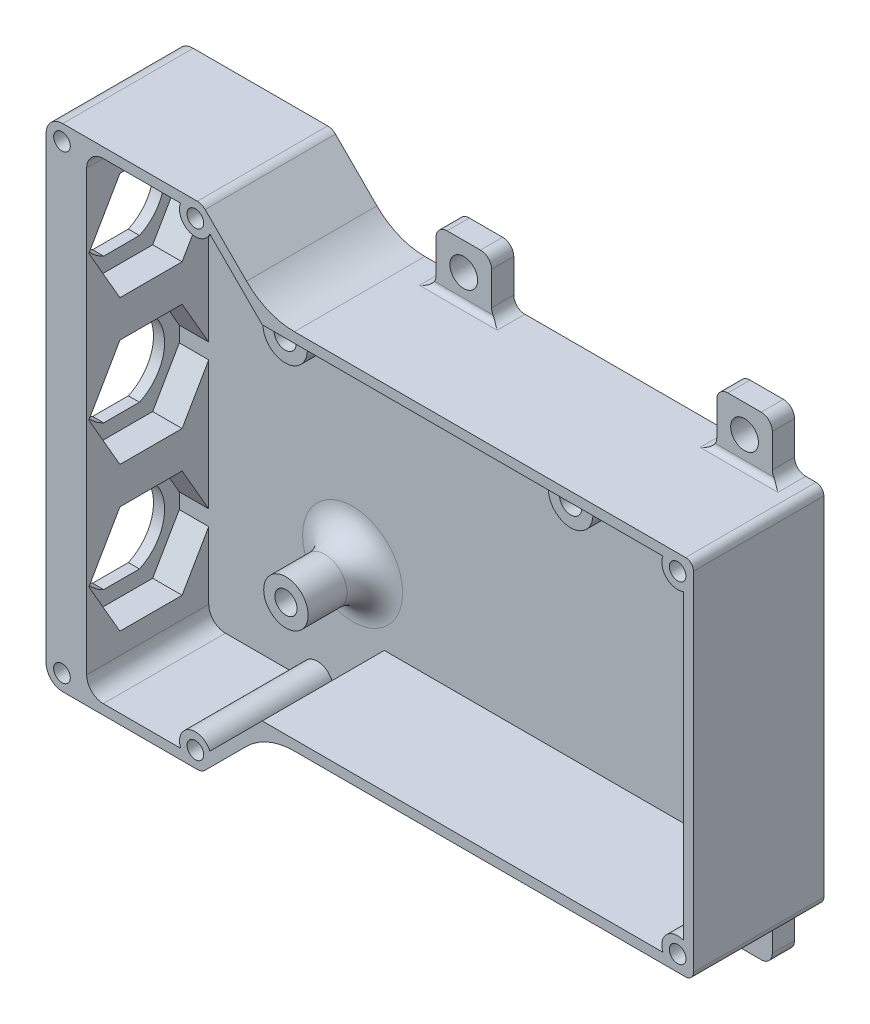
SolidWorks part; units mm, degrees
ref_plane "Front Plane" through (0, 0, 0) normal (0, 0, 1) x (1, 0, 0)
ref_plane "Top Plane" through (0, 0, 0) normal (0, 1, 0) x (1, 0, 0)
ref_plane "Right Plane" through (0, 0, 0) normal (1, 0, 0) x (0, 0, -1)
sketch "Sketch1" plane through (0, 0, 0) normal (0, 0, 1) x (1, 0, 0)
  line L0 (21.6569, -104.2696) -> (33.2669, -92.6596)
  line L1 (21.6569, -11.2696) -> (33.2619, -22.8746)
  line L2 (22.8284, -103.098) -> (34.4384, -91.488) construction
  line L3 (22.8284, -12.4412) -> (34.4334, -24.0462) construction
  line L10 (0, -100.2696) -> (20, -100.2696)
  line L11 (0, -15.2696) -> (20, -15.2696)
  line L12 (20, -100.2696) -> (31.61, -88.6596)
  line L13 (96.455, -88.6596) -> (8, -88.6596) construction
  line L14 (8, -26.8746) -> (96.455, -26.8746) construction
  line L15 (20, -15.2696) -> (31.605, -26.8746)
  line L16 (1.6569, -104.2696) -> (21.6569, -104.2696)
  line L17 (1.6569, -11.2696) -> (21.6569, -11.2696)
  line L24 (96.455, -88.6596) -> (31.61, -88.6596)
  line L26 (31.605, -26.8746) -> (96.455, -26.8746)
  line L27 (96.455, -26.8746) -> (96.455, -88.6596)
  line L28 (100.455, -92.6596) -> (33.2669, -92.6596)
  line L29 (33.2619, -22.8746) -> (100.455, -22.8746)
  line L31 (100.455, -22.8746) -> (100.455, -92.6596)
  line L33 (0, -100.2696) -> (-18.3, -100.2696)
  line L35 (0, -15.2696) -> (-18.3, -15.2696)
  line L36 (-18.3, -15.2696) -> (-18.3, -11.2696)
  line L37 (-18.3, -11.2696) -> (1.6569, -11.2696)
  line L38 (-18.3, -100.2696) -> (-18.3, -104.2696)
  line L39 (-18.3, -104.2696) -> (1.6569, -104.2696)
  line L45 (100.455, -92.6596) -> (4, -92.6596) construction
  line L46 (4, -92.6596) -> (4, -22.8746) construction
  line L47 (4, -22.8746) -> (100.455, -22.8746) construction
  line L52 (8, -88.6596) -> (8, -26.8746) construction
  dimension "D1" = 4
  dimension "D3" = 4
  dimension "D2" = 4
extrude "Boss-Extrude1" add sketch "Sketch1" along normal blind 36.78
sketch "Sketch2" plane through (0, 0, 0) normal (0, 0, -1) x (-1, 0, 0)
  line L0 (18.3, -15.2696) -> (18.3, -100.2696)
  line L16 (-33.2669, -92.6596) -> (-21.6569, -104.2696)
  line L17 (-31.61, -88.6596) -> (-96.455, -88.6596)
  line L18 (-96.455, -88.6596) -> (-96.455, -26.8746)
  line L19 (-96.455, -26.8746) -> (-31.605, -26.8746)
  line L20 (-33.2669, -92.6596) -> (-21.6569, -104.2696)
  line L21 (-20, -15.2696) -> (18.3, -15.2696)
  line L22 (18.3, -15.2696) -> (18.3, -11.2696)
  line L23 (18.3, -11.2696) -> (-21.6569, -11.2696)
  line L24 (-20, -100.2696) -> (-31.61, -88.6596)
  line L25 (-33.2619, -22.8746) -> (-100.455, -22.8746)
  line L26 (-100.455, -22.8746) -> (-100.455, -92.6596)
  line L27 (-100.455, -92.6596) -> (-33.2669, -92.6596)
  line L29 (-21.6569, -104.2696) -> (18.3, -104.2696)
  line L30 (18.3, -104.2696) -> (18.3, -100.2696)
  line L31 (18.3, -100.2696) -> (-20, -100.2696)
  line L33 (-31.605, -26.8746) -> (-20, -15.2696)
  line L35 (-21.6569, -11.2696) -> (-33.2619, -22.8746)
  line L36 (-21.6569, -11.2696) -> (-33.2619, -22.8746)
  line L38 (18.3, -15.2696) -> (18.3, -11.2696)
  line L39 (18.3, -11.2696) -> (-21.6569, -11.2696)
  line L41 (-33.2619, -22.8746) -> (-100.455, -22.8746)
  line L42 (-100.455, -22.8746) -> (-100.455, -92.6596)
  line L43 (-100.455, -92.6596) -> (-33.2669, -92.6596)
  line L45 (-21.6569, -104.2696) -> (18.3, -104.2696)
  line L46 (18.3, -104.2696) -> (18.3, -100.2696)
  dimension "D1" = 0
extrude "Boss-Extrude2" add sketch "Sketch2" against normal blind 3.5
sketch "Sketch4" plane through (-5.3, 0, 0) normal (1, 0, 0) x (0, 0, -1)
  line L0 (-13.8923, -90.5196) -> (-10.7395, -90.5196) construction
  line L1 (-13.8923, -90.5196) -> (-17.0451, -90.5196) construction
  line L2 (-13.8923, -77.0196) -> (-10.7395, -77.0196) construction
  line L3 (-13.8923, -77.0196) -> (-17.0451, -77.0196) construction
  line L4 (-13.8923, -64.5196) -> (-10.7395, -64.5196) construction
  line L5 (-13.8923, -64.5196) -> (-17.0451, -64.5196) construction
  line L6 (-13.8923, -51.0196) -> (-10.7395, -51.0196) construction
  line L7 (-13.8923, -51.0196) -> (-17.0451, -51.0196) construction
  line L8 (-13.8923, -38.5196) -> (-17.0451, -38.5196) construction
  line L9 (-13.8923, -38.5196) -> (-10.7395, -38.5196) construction
  line L10 (-13.8923, -25.0196) -> (-10.7395, -25.0196) construction
  line L11 (-13.8923, -25.0196) -> (-17.0451, -25.0196) construction
  line L12 (-13.8923, -90.5196) -> (-10.7395, -90.5196)
  line L13 (-13.8923, -90.5196) -> (-17.0451, -90.5196)
  line L14 (-13.8923, -77.0196) -> (-10.7395, -77.0196)
  line L15 (-13.8923, -77.0196) -> (-17.0451, -77.0196)
  line L16 (-13.8923, -64.5196) -> (-10.7395, -64.5196)
  line L17 (-13.8923, -64.5196) -> (-17.0451, -64.5196)
  line L18 (-13.8923, -51.0196) -> (-10.7395, -51.0196)
  line L19 (-13.8923, -51.0196) -> (-17.0451, -51.0196)
  line L20 (-13.8923, -38.5196) -> (-17.0451, -38.5196)
  line L21 (-13.8923, -38.5196) -> (-10.7395, -38.5196)
  line L22 (-13.8923, -25.0196) -> (-10.7395, -25.0196)
  line L23 (-13.8923, -25.0196) -> (-17.0451, -25.0196)
  line L24 (-13.8923, -38.8196) -> (-17.111, -38.8196)
  line L25 (-13.8923, -38.8196) -> (-10.6736, -38.8196)
  line L26 (-13.8923, -24.7196) -> (-10.6736, -24.7196)
  line L27 (-13.8923, -24.7196) -> (-17.111, -24.7196)
  line L28 (-13.8923, -64.8196) -> (-17.111, -64.8196)
  line L29 (-13.8923, -64.8196) -> (-10.6736, -64.8196)
  line L30 (-13.8923, -50.7196) -> (-10.6736, -50.7196)
  line L31 (-13.8923, -50.7196) -> (-17.111, -50.7196)
  line L32 (-13.8923, -90.8196) -> (-17.111, -90.8196)
  line L33 (-13.8923, -90.8196) -> (-10.6736, -90.8196)
  line L34 (-13.8923, -76.7196) -> (-10.6736, -76.7196)
  line L35 (-13.8923, -76.7196) -> (-17.111, -76.7196)
  line L36 (-36.78, -100.2696) -> (-3.5, -100.2696)
  line L37 (-36.78, -100.2696) -> (-3.5, -100.2696)
  line L38 (-3.5, -100.2696) -> (-3.5, -15.2696)
  line L39 (-3.5, -100.2696) -> (-3.5, -15.2696)
  line L40 (-3.5, -15.2696) -> (-36.78, -15.2696)
  line L41 (-3.5, -15.2696) -> (-36.78, -15.2696)
  line L42 (-36.78, -15.2696) -> (-36.78, -100.2696)
  arc A0 (-17.0451, -77.0196) -> (-17.0451, -90.5196) centre (-13.8923, -83.7696) ccw construction
  arc A1 (-10.7395, -90.5196) -> (-10.7395, -77.0196) centre (-13.8923, -83.7696) ccw construction
  arc A2 (-10.7395, -64.5196) -> (-10.7395, -51.0196) centre (-13.8923, -57.7696) ccw construction
  arc A3 (-17.0451, -51.0196) -> (-17.0451, -64.5196) centre (-13.8923, -57.7696) ccw construction
  arc A4 (-17.0451, -25.0196) -> (-17.0451, -38.5196) centre (-13.8923, -31.7696) ccw construction
  arc A5 (-10.7395, -38.5196) -> (-10.7395, -25.0196) centre (-13.8923, -31.7696) ccw construction
  arc A6 (-17.0451, -77.0196) -> (-17.0451, -90.5196) centre (-13.8923, -83.7696) ccw
  arc A7 (-10.7395, -90.5196) -> (-10.7395, -77.0196) centre (-13.8923, -83.7696) ccw
  arc A8 (-10.7395, -64.5196) -> (-10.7395, -51.0196) centre (-13.8923, -57.7696) ccw
  arc A9 (-17.0451, -51.0196) -> (-17.0451, -64.5196) centre (-13.8923, -57.7696) ccw
  arc A10 (-17.0451, -25.0196) -> (-17.0451, -38.5196) centre (-13.8923, -31.7696) ccw
  arc A11 (-10.7395, -38.5196) -> (-10.7395, -25.0196) centre (-13.8923, -31.7696) ccw
  arc A12 (-17.111, -24.7196) -> (-17.111, -38.8196) centre (-13.8923, -31.7696) ccw
  arc A13 (-10.6736, -38.8196) -> (-10.6736, -24.7196) centre (-13.8923, -31.7696) ccw
  arc A14 (-17.111, -50.7196) -> (-17.111, -64.8196) centre (-13.8923, -57.7696) ccw
  arc A15 (-10.6736, -64.8196) -> (-10.6736, -50.7196) centre (-13.8923, -57.7696) ccw
  arc A16 (-17.111, -76.7196) -> (-17.111, -90.8196) centre (-13.8923, -83.7696) ccw
  arc A17 (-10.6736, -90.8196) -> (-10.6736, -76.7196) centre (-13.8923, -83.7696) ccw
  line M1 (-21.5451, -64.5196) -> (-18.3923, -64.5196)
  arc M2 (-18.3923, -64.5196) -> (-18.3923, -51.0196) centre (-18.3923, -57.7696) cw
  line M3 (-18.3923, -51.0196) -> (-21.5451, -51.0196)
  arc M4 (-21.5451, -51.0196) -> (-21.5451, -64.5196) centre (-18.3923, -57.7696) ccw
  dimension "D1" = 0.3
extrude "Boss-Extrude3" add sketch "Sketch4" against normal blind 2 contours L41 L42 L37 L39 A17 L33 L32 A16 L35 L34 A15 L29 L28 A14 L31 L30 A13 L25 L24 A12 L27 L26 M1 M4 M3 M2 | M4 M1 M2 M3 region at (-5.3, -57.7696, 35.8672) region at (-5.3, -57.7696, 25.6881)
sketch "Sketch5" plane through (-5.3, 0, 0) normal (1, 0, 0) x (0, 0, -1)
  line L18 (-13.8923, -24.7196) -> (-13.8923, -38.8196)
  line L19 (-10.6736, -24.7196) -> (-17.111, -24.7196) construction
  line L20 (-17.111, -38.8196) -> (-10.6736, -38.8196) construction
  line L21 (-13.8923, -50.7196) -> (-13.8923, -64.8196)
  line L22 (-10.6736, -50.7196) -> (-17.111, -50.7196) construction
  line L23 (-17.111, -64.8196) -> (-10.6736, -64.8196) construction
  line L24 (-13.8923, -76.7196) -> (-13.8923, -90.8196)
  line L25 (-10.6736, -76.7196) -> (-17.111, -76.7196) construction
  line L26 (-17.111, -90.8196) -> (-10.6736, -90.8196) construction
  line L27 (-25.0848, -83.7696) -> (-19.4886, -93.4626)
  line L28 (-24.7384, -31.7696) -> (-19.3154, -41.1626)
  line L29 (-19.3154, -41.1626) -> (-8.4692, -41.1626)
  line L30 (-8.4692, -41.1626) -> (-3.0462, -31.7696)
  line L31 (-3.0462, -31.7696) -> (-8.4692, -22.3766)
  line L32 (-8.4692, -22.3766) -> (-19.3154, -22.3766)
  line L33 (-19.3154, -22.3766) -> (-24.7384, -31.7696)
  line L34 (-24.7384, -57.7696) -> (-19.3154, -67.1626)
  line L35 (-19.3154, -67.1626) -> (-8.4692, -67.1626)
  line L36 (-36.78, -100.2696) -> (-3.5, -100.2696) construction
  line L37 (-36.78, -15.2696) -> (-36.78, -100.2696) construction
  line L38 (-3.5, -15.2696) -> (-36.78, -15.2696) construction
  line L39 (-3.5, -100.2696) -> (-3.5, -15.2696) construction
  line L40 (-36.78, -100.2696) -> (-3.5, -100.2696)
  line L41 (-36.78, -15.2696) -> (-36.78, -100.2696)
  line L42 (-3.5, -15.2696) -> (-36.78, -15.2696)
  line L43 (-3.5, -100.2696) -> (-3.5, -15.2696)
  line L44 (-8.4692, -67.1626) -> (-3.0462, -57.7696)
  line L45 (-3.0462, -57.7696) -> (-8.4692, -48.3766)
  line L46 (-8.4692, -48.3766) -> (-19.3154, -48.3766)
  line L47 (-19.3154, -48.3766) -> (-24.7384, -57.7696)
  line L48 (-24.7384, -83.7696) -> (-19.3154, -93.1626)
  line L49 (-19.3154, -93.1626) -> (-8.4692, -93.1626)
  line L50 (-8.4692, -93.1626) -> (-3.0462, -83.7696)
  line L51 (-3.0462, -83.7696) -> (-8.4692, -74.3766)
  line L52 (-8.4692, -74.3766) -> (-19.3154, -74.3766)
  line L53 (-19.3154, -74.3766) -> (-24.7384, -83.7696)
  line L54 (-19.4886, -93.4626) -> (-8.296, -93.4626)
  line L55 (-8.296, -93.4626) -> (-2.6998, -83.7696)
  line L56 (-2.6998, -83.7696) -> (-8.296, -74.0766)
  line L57 (-8.296, -74.0766) -> (-19.4886, -74.0766)
  line L58 (-19.4886, -74.0766) -> (-25.0848, -83.7696)
  line L59 (-19.4886, -22.0766) -> (-25.0848, -31.7696)
  line L60 (-25.0848, -31.7696) -> (-19.4886, -41.4626)
  line L61 (-19.4886, -41.4626) -> (-8.296, -41.4626)
  line L62 (-8.296, -41.4626) -> (-2.6998, -31.7696)
  line L63 (-2.6998, -31.7696) -> (-8.296, -22.0766)
  line L64 (-8.296, -22.0766) -> (-19.4886, -22.0766)
  line L65 (-19.4886, -48.0766) -> (-25.0848, -57.7696)
  line L66 (-25.0848, -57.7696) -> (-19.4886, -67.4626)
  line L67 (-19.4886, -67.4626) -> (-8.296, -67.4626)
  line L68 (-8.296, -67.4626) -> (-2.6998, -57.7696)
  line L69 (-2.6998, -57.7696) -> (-8.296, -48.0766)
  line L70 (-8.296, -48.0766) -> (-19.4886, -48.0766)
  circle A0 centre (-13.8923, -31.7696) radius 9.393 construction
  circle A1 centre (-13.8923, -57.7696) radius 9.393 construction
  circle A2 centre (-13.8923, -83.7696) radius 9.393 construction
  line M16 (-3.5, -15.2696) -> (-36.78, -15.2696)
  line M17 (-36.78, -15.2696) -> (-36.78, -100.2696)
  line M18 (-36.78, -100.2696) -> (-3.5, -100.2696)
  line M19 (-3.5, -100.2696) -> (-3.5, -15.2696)
  dimension "D1" = 0.3
extrude "Boss-Extrude4" add sketch "Sketch5" along normal up to surface (5.3 mm away) contours L46 L45 L44 L34 L32 L30 L29 L28 M19 M16 M17 M18 region at (-5.3, -89.0725, 23.0772)
sketch "Sketch6" plane through (0, 0, 36.78) normal (0, 0, 1) x (1, 0, 0)
  line L1 (-48.9743, 0) -> (133.8378, 0)
  line L2 (-48.9743, 0) -> (-48.9743, -122.4446)
  line L3 (-48.9743, -122.4446) -> (133.8378, -122.4446)
  line L4 (133.8378, 0) -> (133.8378, -122.4446)
extrude "Cut-Extrude1" cut sketch "Sketch6" against normal blind 4
ref_plane "Plane1" through (5, 0, 0) normal (1, 0, 0) x (0, 0, -1)
fillet "Fillet4" radius 10 2 edges at (33.2669, -92.6596, 16.39) (33.2619, -22.8746, 16.39)
sketch "Sketch8" plane through (0, 0, 32.78) normal (0, 0, 1) x (1, 0, 0)
  line L0 (100.455, -92.6596) -> (100.455, -22.8746) construction
  line L3 (100.455, -88.6596) -> (100.455, -26.8746)
  line L6 (96.455, -26.8746) -> (96.455, -88.6596)
  line L7 (96.455, -26.8746) -> (100.455, -26.8746)
  line L8 (96.455, -88.6596) -> (100.455, -88.6596)
extrude "Cut-Extrude2" cut sketch "Sketch8" against normal up to surface (29.28 mm away) up to face at (13.2163, -57.7691, 3.5)
sketch "Sketch9" plane through (100.455, 0, 0) normal (1, 0, 0) x (0, 0, -1)
  line L0 (-32.78, -92.6596) -> (-32.78, -88.6596) construction
  line L1 (-3.5, -88.6596) -> (-32.78, -88.6596) construction
  line L2 (-32.78, -92.6596) -> (0, -92.6596) construction
  line L3 (0, -92.6596) -> (0, -22.8746) construction
  line L4 (-3.5, -88.6596) -> (-3.5, -26.8746) construction
  line L5 (-3.5, -26.8746) -> (-32.78, -26.8746) construction
  line L6 (-32.78, -26.8746) -> (-32.78, -22.8746) construction
  line L7 (-32.78, -22.8746) -> (0, -22.8746) construction
  line L8 (-32.78, -92.6596) -> (-32.78, -88.6596)
  line L9 (-3.5, -88.6596) -> (-32.78, -88.6596)
  line L10 (-32.78, -92.6596) -> (0, -92.6596)
  line L11 (0, -92.6596) -> (0, -22.8746)
  line L12 (-3.5, -88.6596) -> (-3.5, -26.8746)
  line L13 (-3.5, -26.8746) -> (-32.78, -26.8746)
  line L14 (-32.78, -26.8746) -> (-32.78, -22.8746)
  line L15 (-32.78, -22.8746) -> (0, -22.8746)
extrude "Boss-Extrude6" add sketch "Sketch9" along normal blind 11
sketch "Sketch10" plane through (0, 0, 32.78) normal (0, 0, 1) x (1, 0, 0)
  line L0 (111.455, -88.6596) -> (31.61, -88.6596) construction
  line L2 (31.605, -26.8746) -> (111.455, -26.8746) construction
  line L4 (111.455, -88.6596) -> (107.455, -88.6596)
  line L6 (107.455, -26.8746) -> (111.455, -26.8746)
  line L8 (111.455, -26.8746) -> (107.455, -26.8746)
  line L9 (107.455, -26.8746) -> (107.455, -88.6596)
  line L10 (111.455, -26.8746) -> (111.455, -88.6596)
  line M1 (31.605, -26.8746) -> (111.455, -26.8746)
  line M19 (111.455, -88.6596) -> (31.61, -88.6596)
extrude "Boss-Extrude7" add sketch "Sketch10" against normal up to surface (29.28 mm away) contours L10 L9 M1 M19 region at (109.455, -57.7671, 32.78) up to face at (-12.8, -57.7696, 3.5)
sketch "Sketch24" plane through (0, 0, 32.78) normal (0, 0, 1) x (1, 0, 0)
  line L2 (111.455, -22.8746) -> (37.404, -22.8746) construction
  line L3 (111.455, -22.8746) -> (111.455, -92.6596) construction
  line L4 (31.605, -26.8746) -> (107.455, -26.8746) construction
  line L5 (107.455, -26.8746) -> (107.455, -88.6596) construction
  line L6 (111.455, -22.8746) -> (37.404, -22.8746)
  line L7 (111.455, -22.8746) -> (111.455, -92.6596)
  line L8 (31.605, -26.8746) -> (107.455, -26.8746)
  line L9 (107.455, -26.8746) -> (107.455, -88.6596)
  line L10 (107.455, -26.8746) -> (107.455, -29.8746)
  line L11 (107.455, -26.8746) -> (104.455, -26.8746)
  line L12 (104.455, -26.8746) -> (107.455, -29.8746)
  line L13 (107.455, -88.6596) -> (104.455, -88.6596)
  line L14 (107.455, -88.6596) -> (31.61, -88.6596) construction
  line L15 (104.455, -88.6596) -> (107.455, -85.6596)
  line M1 (107.455, -26.8746) -> (107.455, -88.6596)
  line M2 (107.455, -88.6596) -> (31.61, -88.6596)
extrude "Boss-Extrude10" add sketch "Sketch24" against normal up to surface (29.28 mm away) contours L15 M2 M1 | L8 L12 M1 region at (106.455, -87.6596, 32.78) region at (106.455, -27.8746, 32.78) up to face at (-12.8, -57.7696, 3.5)
sketch "Sketch28" plane through (0, 0, 32.78) normal (0, 0, 1) x (1, 0, 0)
  line L1 (-7.3, -83.7696) -> (-7.3, -31.7696)
  line L2 (-7.3, -31.7696) -> (-7.3, -6.2489)
  line L3 (-7.3, -6.2489) -> (-26.3455, -6.2489)
  line L4 (-26.3455, -6.2489) -> (-26.3455, -107.7031)
  line L5 (-26.3455, -107.7031) -> (-7.3, -107.7031)
  line L6 (-7.3, -107.7031) -> (-7.3, -83.7696)
extrude "Cut-Extrude12" cut sketch "Sketch28" against normal through all
sketch "Sketch29" plane through (0, 0, 32.78) normal (0, 0, 1) x (1, 0, 0)
  line L0 (-7.3, -104.2696) -> (21.6569, -104.2696) construction
  line L1 (21.6569, -104.2696) -> (30.3379, -95.5885) construction
  line L2 (37.409, -92.6596) -> (111.455, -92.6596) construction
  line L3 (111.455, -22.8746) -> (111.455, -92.6596) construction
  line L4 (111.455, -22.8746) -> (37.404, -22.8746) construction
  line L5 (30.3329, -19.9457) -> (21.6569, -11.2696) construction
  line L6 (21.6569, -11.2696) -> (-7.3, -11.2696) construction
  line L7 (-7.3, -104.2696) -> (21.6569, -104.2696)
  line L8 (21.6569, -104.2696) -> (30.3379, -95.5885)
  line L9 (37.409, -92.6596) -> (111.455, -92.6596)
  line L10 (111.455, -22.8746) -> (111.455, -92.6596)
  line L11 (111.455, -22.8746) -> (37.404, -22.8746)
  line L12 (30.3329, -19.9457) -> (21.6569, -11.2696)
  line L13 (21.6569, -11.2696) -> (-7.3, -11.2696)
  line L14 (-7.3, -102.0736) -> (20.7472, -102.0736)
  line L15 (20.7472, -102.0736) -> (28.7851, -94.0357)
  line L16 (37.409, -90.4636) -> (109.259, -90.4636)
  line L17 (109.259, -25.0706) -> (109.259, -90.4636)
  line L18 (109.259, -25.0706) -> (37.404, -25.0706)
  line L19 (28.7801, -21.4985) -> (20.7472, -13.4656)
  line L20 (20.7472, -13.4656) -> (-7.3, -13.4656)
  line L21 (-7.3, -13.4656) -> (-7.3, -11.2696)
  line L22 (-7.3, -102.0736) -> (-7.3, -104.2696)
  arc A0 (37.409, -92.6596) -> (30.3379, -95.5885) centre (37.409, -102.6596) ccw construction
  arc A1 (30.3329, -19.9457) -> (37.404, -22.8746) centre (37.404, -12.8746) ccw construction
  arc A2 (37.409, -92.6596) -> (30.3379, -95.5885) centre (37.409, -102.6596) ccw
  arc A3 (30.3329, -19.9457) -> (37.404, -22.8746) centre (37.404, -12.8746) ccw
  arc A4 (37.409, -90.4636) -> (28.7851, -94.0357) centre (37.409, -102.6596) ccw
  arc A5 (28.7801, -21.4985) -> (37.404, -25.0706) centre (37.404, -12.8746) ccw
  dimension "D1" = 2.196
extrude "Cut-Extrude13" cut sketch "Sketch29" against normal through all
sketch "Sketch30" plane through (0, 0, 0) normal (0, 0, -1) x (-1, 0, 0)
  line L0 (-37.404, -25.0706) -> (-109.259, -25.0706) construction
  line L1 (-109.259, -25.0706) -> (-109.259, -90.4636) construction
  line L2 (-109.259, -90.4636) -> (-37.409, -90.4636) construction
  line L3 (-28.7851, -94.0357) -> (-20.7472, -102.0736) construction
  line L4 (-20.7472, -102.0736) -> (7.3, -102.0736) construction
  line L5 (7.3, -102.0736) -> (7.3, -13.4656) construction
  line L6 (7.3, -13.4656) -> (-20.7472, -13.4656) construction
  line L7 (-20.7472, -13.4656) -> (-28.7801, -21.4985) construction
  line L8 (-109.259, -25.0706) -> (-109.259, -90.4636)
  line L9 (-109.259, -90.4636) -> (-37.409, -90.4636)
  line L10 (-28.7851, -94.0357) -> (-20.7472, -102.0736)
  line L11 (-20.7472, -102.0736) -> (7.3, -102.0736)
  line L12 (7.3, -102.0736) -> (7.3, -13.4656)
  line L13 (7.3, -13.4656) -> (-20.7472, -13.4656)
  line L14 (-20.7472, -13.4656) -> (-28.7801, -21.4985)
  line L15 (-37.404, -25.0706) -> (-109.259, -25.0706)
  arc A0 (-28.7851, -94.0357) -> (-37.409, -90.4636) centre (-37.409, -102.6596) ccw construction
  arc A1 (-37.404, -25.0706) -> (-28.7801, -21.4985) centre (-37.404, -12.8746) ccw construction
  arc A2 (-28.7851, -94.0357) -> (-37.409, -90.4636) centre (-37.409, -102.6596) ccw
  arc A3 (-37.404, -25.0706) -> (-28.7801, -21.4985) centre (-37.404, -12.8746) ccw
extrude "Cut-Extrude14" cut sketch "Sketch30" against normal blind 2
fillet "Fillet26" radius 3 2 edges at (-7.3, -13.4656, 17.39) (-7.3, -102.0736, 17.39)
fillet "Fillet27" radius 3 2 edges at (0, -100.2696, 18.14) (0, -15.2696, 18.14)
fillet "Fillet28" radius 2 4 edges at (20, -15.2696, 18.14) (20.7472, -13.4656, 17.39) (20, -100.2696, 18.14) (20.7472, -102.0736, 17.39) tangent propagation no
sketch "Sketch33" plane through (0, 0, 32.78) normal (0, 0, 1) x (1, 0, 0)
  line L2 (109.259, -25.0706) -> (109.259, -90.4636) construction
  line L3 (109.259, -90.4636) -> (37.409, -90.4636) construction
  line L4 (19.9188, -102.0736) -> (-4.3, -102.0736) construction
  line L5 (28.7851, -94.0357) -> (21.333, -101.4878) construction
  line L6 (-4.3, -13.4656) -> (19.9188, -13.4656) construction
  line L7 (21.333, -14.0514) -> (28.7801, -21.4985) construction
  line L8 (-7.3, -99.0736) -> (-7.3, -16.4656) construction
  line L9 (37.404, -25.0706) -> (109.259, -25.0706) construction
  circle A0 centre (106.406, -27.9236) radius 1.5
  circle A1 centre (106.406, -27.9236) radius 2.853
  circle A2 centre (106.406, -87.6106) radius 2.853
  circle A3 centre (19.5655, -99.2206) radius 2.853
  circle A4 centre (19.5655, -16.3186) radius 2.853
  circle A5 centre (-4.447, -16.3186) radius 2.853
  circle A6 centre (-4.447, -99.2206) radius 2.853
  dimension "D3" = 3
  dimension "D4" = 5.706
  dimension "D2" = 2.853
extrude "Boss-Extrude13" add sketch "Sketch33" against normal up to surface (29.28 mm away) contours A4 | A3 | A2 | A1 up to face at (20.7548, -57.769, 3.5)
sketch "Sketch34" plane through (0, 0, 32.78) normal (0, 0, 1) x (1, 0, 0)
  circle A0 centre (106.406, -27.9236) radius 2.853 construction
  circle A1 centre (106.406, -87.6106) radius 2.853 construction
  circle A2 centre (19.5655, -99.2206) radius 2.853 construction
  circle A3 centre (-4.447, -99.2206) radius 2.853 construction
  circle A4 centre (19.5655, -16.3186) radius 2.853 construction
  circle A5 centre (-4.447, -16.3186) radius 2.853 construction
  circle A6 centre (106.406, -27.9236) radius 2.853
  circle A7 centre (106.406, -87.6106) radius 2.853
  circle A8 centre (19.5655, -99.2206) radius 2.853
  circle A9 centre (-4.447, -99.2206) radius 2.853
  circle A10 centre (19.5655, -16.3186) radius 2.853
  circle A11 centre (-4.447, -16.3186) radius 2.853
  circle A12 centre (-4.447, -16.3186) radius 1.5
  circle A13 centre (19.5655, -16.3186) radius 1.5
  circle A14 centre (106.406, -27.9236) radius 1.5
  circle A15 centre (106.406, -87.6106) radius 1.5
  circle A16 centre (19.5655, -99.2206) radius 1.5
  circle A17 centre (-4.447, -99.2206) radius 1.5
extrude "Cut-Extrude15" cut sketch "Sketch34" against normal blind 20 contours A12 | A13 | A14 | A15 | A16 | A17
fillet "Fillet29" radius 1.425 2 edges at (109.259, -25.0706, 17.39) (109.259, -90.4636, 17.39)
ref_plane "Plane2" through (0, 0, 20.78) normal (0, 0, 1) x (1, 0, 0)
sketch "Sketch35" plane through (0, 0, 20.78) normal (0, 0, 1) x (1, 0, 0)
  line L0 (31.61, -88.6596) -> (103.7528, -88.6596) construction
  line L1 (107.455, -30.5767) -> (107.455, -84.9574) construction
  line L2 (103.7528, -26.8746) -> (31.605, -26.8746) construction
  line L3 (31.61, -88.6596) -> (103.7528, -88.6596)
  line L4 (107.455, -30.5767) -> (107.455, -84.9574)
  line L5 (103.7528, -26.8746) -> (31.605, -26.8746)
  line L6 (107.455, -84.9574) -> (107.455, -88.6596)
  line L7 (107.455, -88.6596) -> (103.7528, -88.6596)
  line L8 (103.7528, -26.8746) -> (107.455, -26.8746)
  line L9 (107.455, -26.8746) -> (107.455, -30.5767)
  line L10 (31.605, -26.8746) -> (31.61, -88.6596)
extrude "Cut-Extrude16" cut sketch "Sketch35" against normal up to surface (17.28 mm away) up to face at (20.4692, -57.769, 3.5)
sketch "Sketch36" plane through (0, 0, 32.78) normal (0, 0, 1) x (1, 0, 0)
  line L1 (-22.7026, -2.6518) -> (121.9699, -2.6518)
  line L2 (-22.7026, -2.6518) -> (-22.7026, -112.3259)
  line L3 (-22.7026, -112.3259) -> (121.9699, -112.3259)
  line L4 (121.9699, -2.6518) -> (121.9699, -112.3259)
extrude "Cut-Extrude17" cut sketch "Sketch36" against normal blind 7.3
sketch "Sketch38" plane through (0, 0, 3.5) normal (0, 0, 1) x (1, 0, 0)
  circle A2 centre (25.7592, -36.7486) radius 2
  circle A4 centre (77.1688, -36.7486) radius 2
  circle A6 centre (25.8989, -78.0236) radius 2
  circle A7 centre (102.7085, -78.0236) radius 4
  circle A8 centre (102.7085, -78.0236) radius 2
  circle A9 centre (77.1688, -36.7486) radius 4
  circle A10 centre (25.7592, -36.7486) radius 4
  circle A11 centre (25.8989, -78.0236) radius 4
  dimension "D1" = 2
extrude "Boss-Extrude14" add sketch "Sketch38" along normal up to surface (12 mm away) contours A7 A8 | A11 A6 | A10 A2 | A9 A4 region at (98.8216, -78.0236, 3.5) region at (73.2819, -36.7486, 3.5) region at (21.8723, -36.7486, 3.5) region at (22.012, -78.0236, 3.5)
fillet "Fillet30" radius 5 4 edges at (98.7085, -78.0236, 3.5) (73.1688, -36.7486, 3.5) (21.7592, -36.7486, 3.5) (21.8989, -78.0236, 3.5)
sketch "Sketch39" plane through (0, 0, 2) normal (0, 0, -1) x (-1, 0, 0)
  line L0 (-107.834, -90.4636) -> (-37.409, -90.4636) construction
  line L1 (-37.404, -25.0706) -> (-107.834, -25.0706) construction
  line L2 (-107.834, -90.4636) -> (-37.409, -90.4636)
  line L3 (-37.404, -25.0706) -> (-107.834, -25.0706)
  line L4 (-103.9747, -25.0706) -> (-103.9747, -15.0706)
  line L5 (-103.9747, -15.0706) -> (-93.9747, -15.0706)
  line L6 (-93.9747, -15.0706) -> (-93.9747, -25.0706)
  line L7 (-53.4219, -25.0706) -> (-53.4219, -15.0706)
  line L8 (-53.4219, -15.0706) -> (-43.4219, -15.0706)
  line L9 (-43.4219, -15.0706) -> (-43.4219, -25.0706)
  line L10 (-109.259, -57.7671) -> (-21.9967, -57.7671)
  line L11 (-109.259, -26.4956) -> (-109.259, -89.0386) construction
  line L12 (-37.404, -90.4636) -> (-107.834, -90.4636)
  line L13 (-43.4219, -100.4636) -> (-43.4219, -90.4636)
  line L14 (-53.4219, -100.4636) -> (-43.4219, -100.4636)
  line L15 (-53.4219, -90.4636) -> (-53.4219, -100.4636)
  line L16 (-103.9747, -90.4636) -> (-103.9747, -100.4636)
  line L17 (-103.9747, -100.4636) -> (-93.9747, -100.4636)
  line L18 (-93.9747, -100.4636) -> (-93.9747, -90.4636)
  circle A0 centre (-98.9747, -20.0706) radius 2.5
  circle A1 centre (-48.4219, -20.0706) radius 2.5
  circle A2 centre (-48.4219, -95.4636) radius 2.5
  circle A3 centre (-98.9747, -95.4636) radius 2.5
extrude "Boss-Extrude15" add sketch "Sketch39" against normal blind 4 contours L9 L8 L7 L3 A1 | L6 L5 L4 L3 A0 | L17 L18 L12 L16 A3 | L12 L15 L14 L13 A2 region at (48.4219, -90.605, 2) region at (98.9747, -90.605, 2) region at (98.9747, -24.9292, 2) region at (48.4219, -24.9292, 2)
fillet "Fillet31" radius 2 16 edges at (53.4219, -100.4636, 4) (53.4219, -90.4636, 4) (43.4219, -90.4636, 4) (43.4219, -100.4636, 4) (93.9747, -90.4636, 4) (93.9747, -100.4636, 4) (103.9747, -100.4636, 4) (103.9747, -90.4636, 4) (103.9747, -25.0706, 4) (103.9747, -15.0706, 4) (93.9747, -15.0706, 4) (93.9747, -25.0706, 4) (43.4219, -25.0706, 4) (53.4219, -25.0706, 4) (43.4219, -15.0706, 4) (53.4219, -15.0706, 4)
fillet "Fillet32" radius 1 4 edges at (48.4219, -25.0706, 6) (98.9747, -25.0706, 6) (98.9747, -90.4636, 6) (48.4219, -90.4636, 6)
